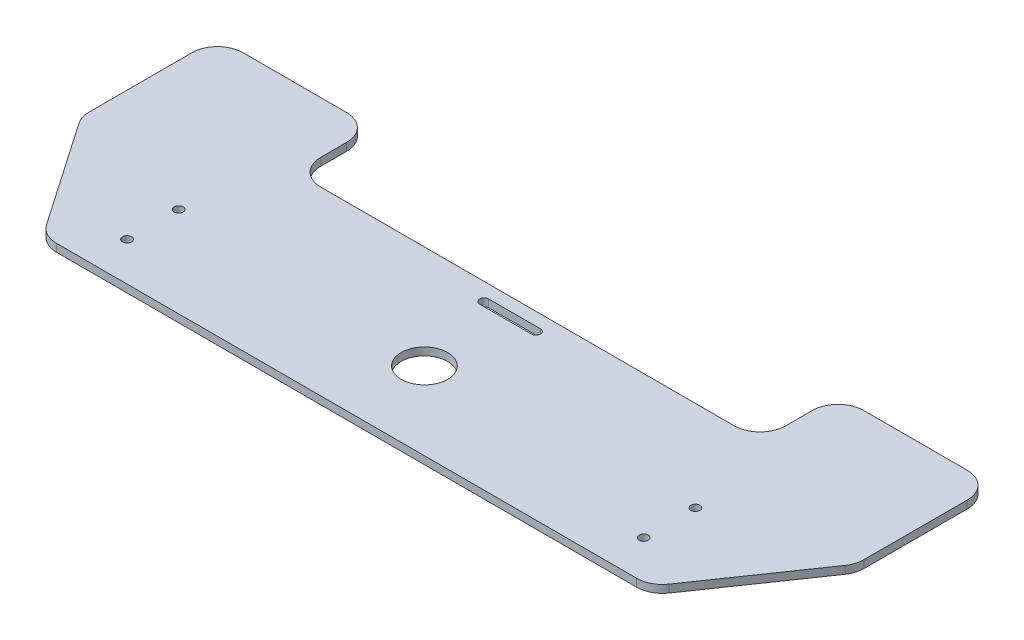
SolidWorks part; units mm, degrees
ref_plane "前视基准面" through (0, 0, 0) normal (0, 0, 1) x (1, 0, 0)
ref_plane "上视基准面" through (0, 0, 0) normal (0, 1, 0) x (1, 0, 0)
ref_plane "右视基准面" through (0, 0, 0) normal (1, 0, 0) x (0, 0, -1)
other "Configuration Table"
sketch "草图1" plane through (0, 0, 0) normal (0, 1, 0) x (1, 0, 0)
  line L5 (-148.2358, 19.5134) -> (-120.4921, -20.7712)
  line L6 (-150, 25.1854) -> (-150, 65)
  line L8 (0, 0) -> (0, 50000) construction
  line L13 (-140.0992, 74.9008) -> (-100, 74.9008)
  line L14 (0, 0.3213) -> (-0.1034, 0.2697) construction
  line L15 (-150, 74.9008) -> (-146.0376, 72.9222) construction
  line L16 (-90, 64.9008) -> (-90, 54.9008)
  line L17 (-80, 44.9008) -> (80, 44.9008)
  line L18 (-112.2563, -25.0992) -> (112.2563, -25.0992)
  line L19 (149.8966, 75.1705) -> (145.9342, 73.1919) construction
  line L20 (0, 0.2309) -> (-0.1034, 0.2697) construction
  line L21 (90, 64.9008) -> (90, 54.9008)
  line L22 (140.1011, 75.0927) -> (100.0019, 75.0927)
  line L23 (150, 25.1854) -> (150, 65)
  line L24 (148.2358, 19.5134) -> (120.4921, -20.7712)
  arc A10 (-90, 54.9008) -> (-80, 44.9008) centre (-80, 54.9008) ccw
  arc A11 (-90, 64.9008) -> (-100, 74.9008) centre (-100, 64.9008) ccw
  arc A12 (-150, 65) -> (-140.0992, 74.9008) centre (-140.0992, 65) cw
  arc A13 (-148.2358, 19.5134) -> (-150, 25.1854) centre (-140, 25.1854) cw
  arc A14 (-120.4921, -20.7712) -> (-112.2563, -25.0992) centre (-112.2563, -15.0992) ccw
  arc A15 (120.4921, -20.7712) -> (112.2563, -25.0992) centre (112.2563, -15.0992) cw
  arc A16 (148.2358, 19.5134) -> (150, 25.1854) centre (140, 25.1854) ccw
  arc A17 (150, 65) -> (140.1011, 75.0927) centre (140.1011, 65.1919) ccw
  arc A18 (90, 64.9008) -> (100.0019, 75.0927) centre (99.9982, 65.0927) cw
  arc A19 (90, 54.9008) -> (80, 44.9008) centre (80, 54.9008) cw
  point P0 (0, 0)
  point P17 (0, 25.2697)
  point P39 (0, 44.9008)
  point P40 (0, -25.0992)
  dimension "D1" = 60
extrude "凸台-拉伸1" add sketch "草图1" along normal blind 3
sketch "草图2" plane through (0, 3, 0) normal (0, 1, 0) x (1, 0, 0)
  line L1 (102.5393, 24.9008) -> (97.4607, 24.9008) construction
  line L2 (100, 24.9008) -> (100, -49975.0992) construction
  line L3 (-112.2563, -25.0992) -> (112.2563, -25.0992) construction
  line L4 (0, 0) -> (0, 50000) construction
  circle A0 centre (100, 9.9008) radius 1.75
  circle A1 centre (100, -10.0992) radius 1.75
  circle A2 centre (-100, -10.0992) radius 1.75
  circle A3 centre (-100, 9.9008) radius 1.75
  point P8 (100, 24.9008)
  dimension "D1" = 3.5
  dimension "D3" = 3.5
  dimension "D4" = 15
  dimension "D2" = 15
extrude "切除-拉伸1" cut sketch "草图2" against normal blind 10
sketch "草图3" plane through (0, 3, 0) normal (0, 1, 0) x (1, 0, 0)
  line L0 (-10, 38.1508) -> (10, 38.1508) construction
  line L1 (-10, 39.9008) -> (10, 39.9008)
  line L2 (-10, 36.4008) -> (10, 36.4008)
  line L3 (0, 0) -> (0, 50000) construction
  line L4 (80, 44.9008) -> (-80, 44.9008) construction
  arc A0 (-10, 39.9008) -> (-10, 36.4008) centre (-10, 38.1508) ccw
  arc A1 (10, 36.4008) -> (10, 39.9008) centre (10, 38.1508) ccw
  point P2 (0, 38.1508)
  dimension "D1" = 1.75
  dimension "D2" = 20
  dimension "D3" = 5
extrude "切除-拉伸2" cut sketch "草图3" against normal blind 3
sketch "草图4" plane through (0, 3, 0) normal (0, 1, 0) x (1, 0, 0)
  line L1 (-28.2843, 33.2843) -> (0, 5) construction
  line L3 (0, 5) -> (-28.2843, -23.2843) construction
  circle A0 centre (0, 5) radius 9
  dimension "D1" = 18
  dimension "D2" = 5
  dimension "D3" = 18
extrude "切除-拉伸3" cut sketch "草图4" against normal blind 10
